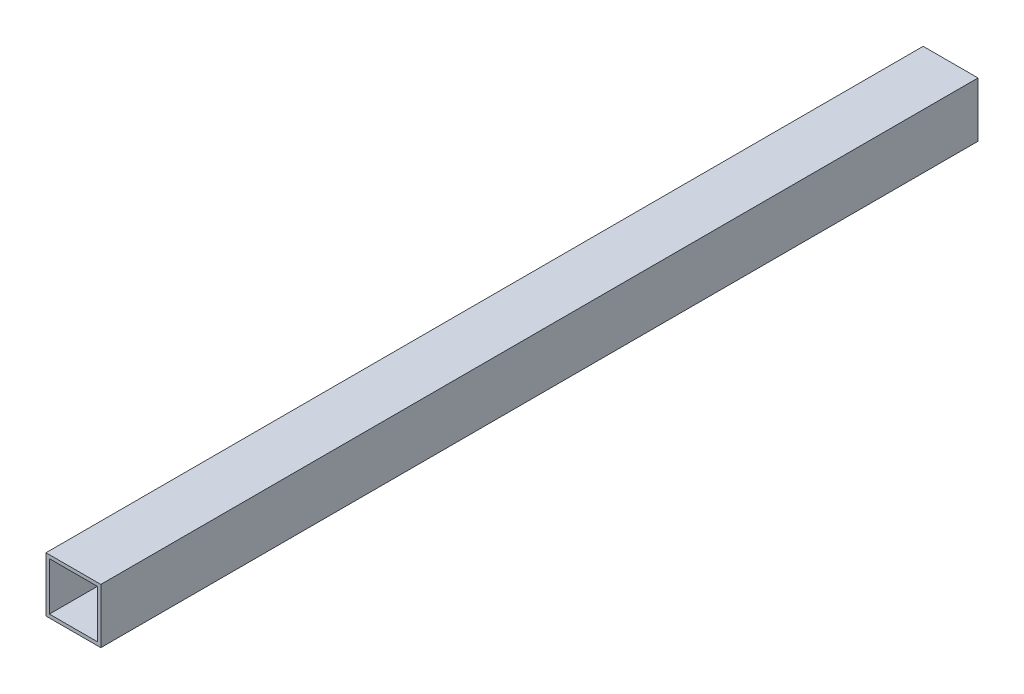
SolidWorks part; units mm, degrees
ref_plane "Front Plane" through (0, 0, 0) normal (0, 0, 1) x (1, 0, 0)
ref_plane "Top Plane" through (0, 0, 0) normal (0, 1, 0) x (1, 0, 0)
ref_plane "Right Plane" through (0, 0, 0) normal (1, 0, 0) x (0, 0, -1)
sketch "Sketch1" plane through (0, 0, 0) normal (0, 0, 1) x (1, 0, 0)
  line L1 (-12.7, -12.7) -> (12.7, -12.7)
  line L2 (-12.7, -12.7) -> (-12.7, 12.7)
  line L3 (-12.7, 12.7) -> (12.7, 12.7)
  line L4 (12.7, -12.7) -> (12.7, 12.7)
  line L5 (-12.7, -12.7) -> (12.7, 12.7) construction
  line L6 (-12.7, 12.7) -> (12.7, -12.7) construction
  point P0 (0, 0)
  dimension "D1" = 25.4
  dimension "D2" = 25.4
extrude "Boss-Extrude1" add sketch "Sketch1" along normal mid plane 406.4
shell "Shell1" thickness 1.5875 removed face at (0, 0, -203.2) removed face at (0, 0, 203.2)
